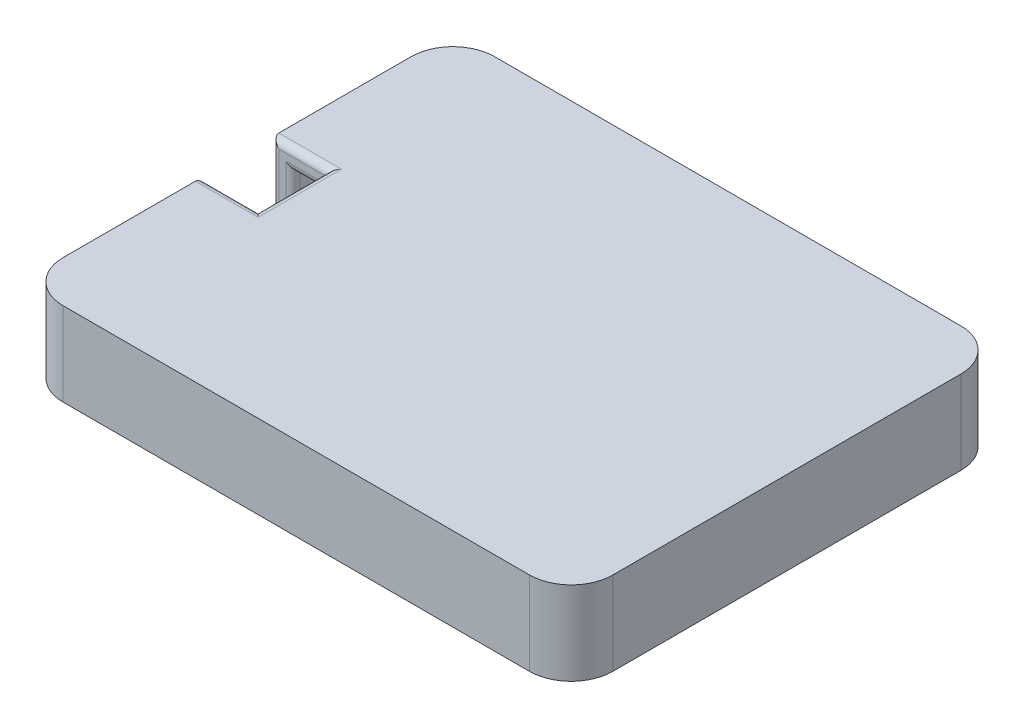
SolidWorks part; units mm, degrees
ref_plane "Plano frontal" through (0, 0, 0) normal (0, 0, 1) x (1, 0, 0)
ref_plane "Plano superior" through (0, 0, 0) normal (0, 1, 0) x (1, 0, 0)
ref_plane "Plano direito" through (0, 0, 0) normal (1, 0, 0) x (0, 0, -1)
sketch "Esboço2" plane through (0, 5.9977, 0) normal (0, 1, 0) x (1, 0, 0)
  line L0 (14.4416, -52.5207) -> (-52.5584, -52.5207) construction
  line L1 (-52.5584, -108.5207) -> (14.4416, -108.5207) construction
  line L2 (17.4416, -105.5207) -> (17.4416, -55.5207) construction
  line L3 (-55.5584, -55.5207) -> (-55.5584, -105.5207) construction
  line L4 (-58.5584, -55.5207) -> (-58.5584, -105.5207)
  line L5 (-52.5584, -111.5207) -> (14.4416, -111.5207)
  line L6 (20.4416, -105.5207) -> (20.4416, -55.5207)
  line L7 (14.4416, -49.5207) -> (-52.5584, -49.5207)
  arc A0 (14.4416, -108.5207) -> (17.4416, -105.5207) centre (14.4416, -105.5207) ccw construction
  arc A1 (17.4416, -55.5207) -> (14.4416, -52.5207) centre (14.4416, -55.5207) ccw construction
  arc A2 (-52.5584, -52.5207) -> (-55.5584, -55.5207) centre (-52.5584, -55.5207) ccw construction
  arc A3 (-55.5584, -105.5207) -> (-52.5584, -108.5207) centre (-52.5584, -105.5207) ccw construction
  arc A4 (14.4416, -108.5207) -> (17.4416, -105.5207) centre (14.4416, -105.5207) ccw construction
  arc A5 (17.4416, -55.5207) -> (14.4416, -52.5207) centre (14.4416, -55.5207) ccw construction
  arc A6 (-52.5584, -52.5207) -> (-55.5584, -55.5207) centre (-52.5584, -55.5207) ccw construction
  arc A7 (-55.5584, -105.5207) -> (-52.5584, -108.5207) centre (-52.5584, -105.5207) ccw construction
  arc A8 (-58.5584, -105.5207) -> (-52.5584, -111.5207) centre (-52.5584, -105.5207) ccw
  arc A9 (14.4416, -111.5207) -> (20.4416, -105.5207) centre (14.4416, -105.5207) ccw
  arc A10 (20.4416, -55.5207) -> (14.4416, -49.5207) centre (14.4416, -55.5207) ccw
  arc A11 (-52.5584, -49.5207) -> (-58.5584, -55.5207) centre (-52.5584, -55.5207) ccw
  dimension "D1" = 3
extrude "Ressalto-extrusão1" add sketch "Esboço2" against normal blind 12
shell "Casca1" thickness 3 removed face at (-19.0584, -6.0023, 80.5207)
sketch "Esboço3" plane through (0, 5.9977, 0) normal (0, 1, 0) x (1, 0, 0)
  line L0 (-58.5584, -75.5207) -> (-50.5584, -75.5207)
  line L1 (-58.5584, -55.5207) -> (-58.5584, -105.5207) construction
  line L2 (-50.5584, -75.5207) -> (-50.5584, -85.5207)
  line L3 (-50.5584, -85.5207) -> (-58.5584, -85.5207)
  line L4 (-58.5584, -75.5207) -> (-58.5584, -85.5207)
  point P6 (-50.5584, -80.5207)
  point P7 (-58.5584, -80.5207)
  dimension "D1" = 10
  dimension "D2" = 8
extrude "Corte-extrusão2" cut sketch "Esboço3" against normal through all
fillet "Filete1" radius 1 10 edges at (-50.5584, 2.9977, 80.5207) (-53.0584, 2.9977, 85.5207) (-53.0584, 2.9977, 75.5207) (-54.5584, 5.9977, 85.5207) (-50.5584, 5.9977, 80.5207) (-54.5584, 5.9977, 75.5207) (-55.5584, -1.5023, 85.5207) (-55.5584, -1.5023, 75.5207) (-58.5584, -0.0023, 75.5207) (-58.5584, -0.0023, 85.5207)
